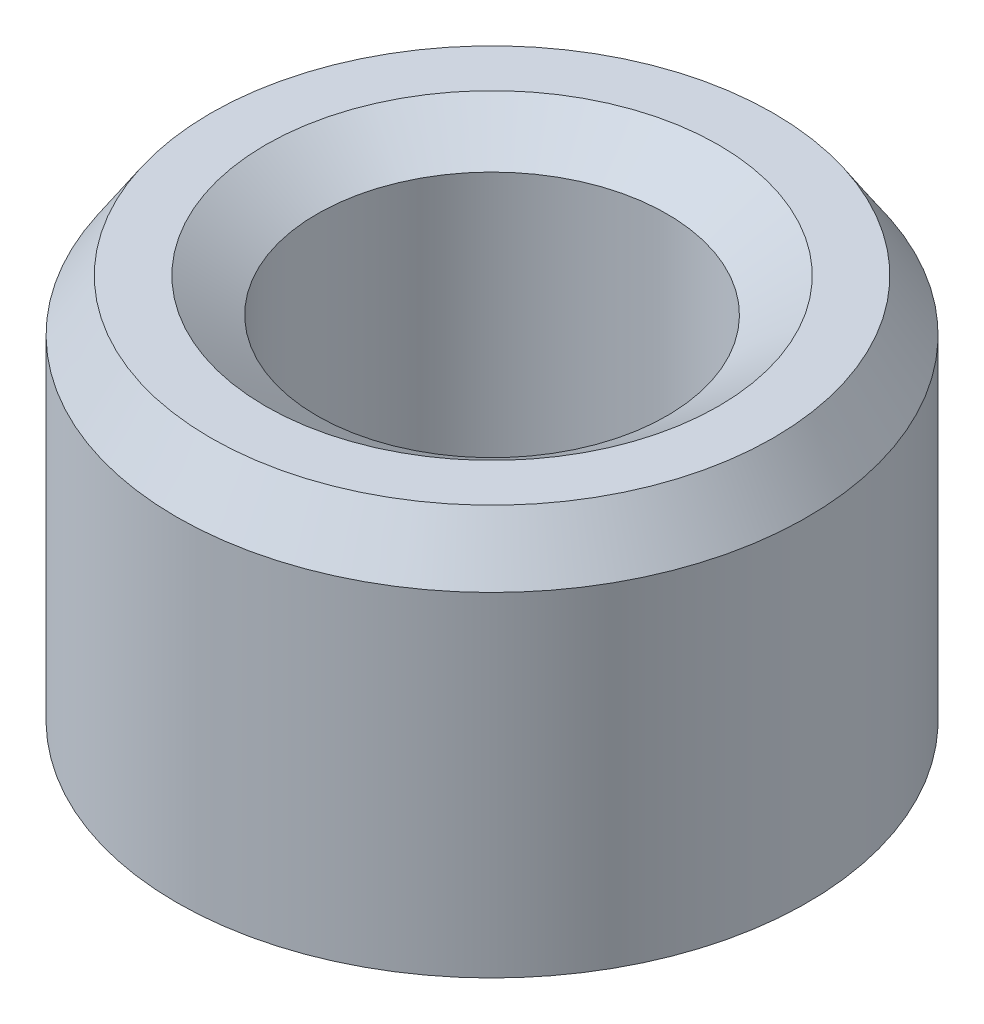
SolidWorks part; units mm, degrees
ref_plane "Front Plane" through (0, 0, 0) normal (0, 0, 1) x (1, 0, 0)
ref_plane "Top Plane" through (0, 0, 0) normal (0, 1, 0) x (1, 0, 0)
ref_plane "Right Plane" through (0, 0, 0) normal (1, 0, 0) x (0, 0, -1)
sketch "Sketch1" plane through (0, 0, 0) normal (0, 1, 0) x (1, 0, 0)
  circle A0 centre (0, 0) radius 5
  dimension "SLEEVE_OD" = 10
extrude "Boss-Extrude1" add sketch "Sketch1" along normal blind 6.6496
sketch "Sketch2" plane through (0, 0, 0) normal (0, 1, 0) x (1, 0, 0)
  circle A0 centre (0, 0) radius 2.7734
  dimension "BORE_D" = 5.5468
extrude "Cut-Extrude1" cut sketch "Sketch2" along normal through all
chamfer "Chamfer1" distance 0.8163 angle 33.503 4 edges at (0, 6.6496, 2.7734) (0, 0, 2.7734) (0, 0, 5) (0, 6.6496, 5) first distance on face at (0, 6.6496, 2.7734) first distance on face at (0, 0, 2.7734) first distance on face at (0, 6.6496, 5)
